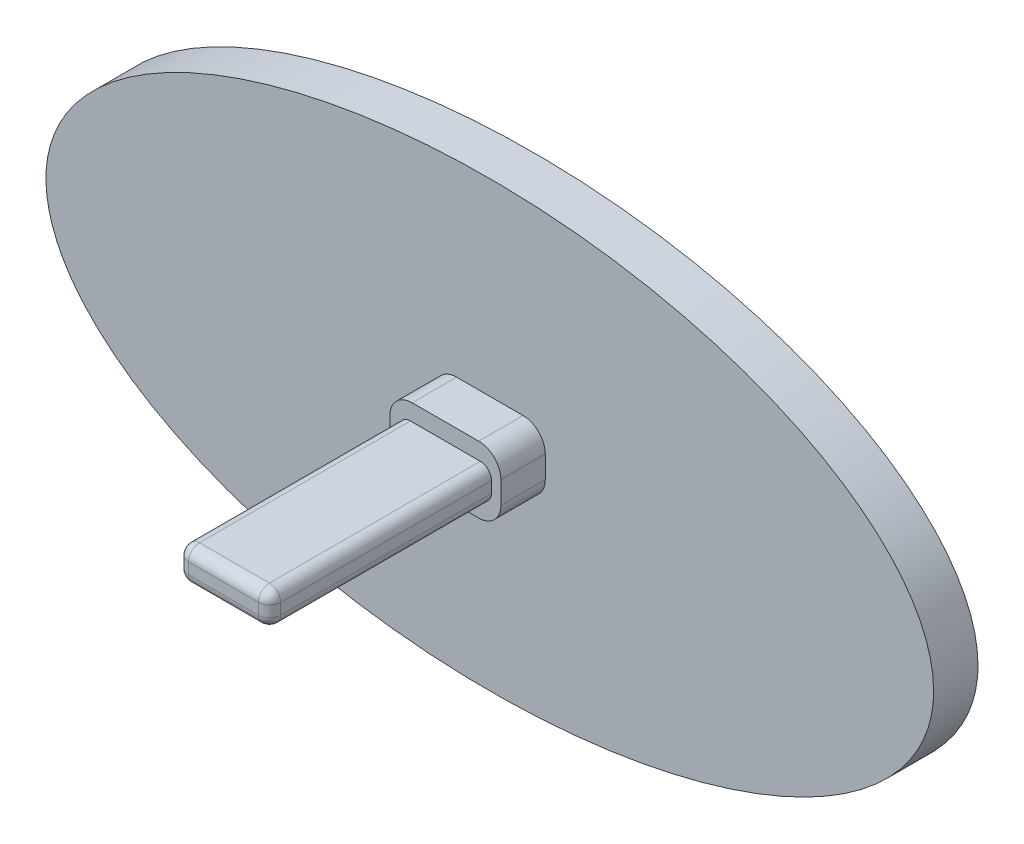
SolidWorks part; units mm, degrees
ref_plane "Front Plane" through (0, 0, 0) normal (0, 0, 1) x (1, 0, 0)
ref_plane "Top Plane" through (0, 0, 0) normal (0, 1, 0) x (1, 0, 0)
ref_plane "Right Plane" through (0, 0, 0) normal (1, 0, 0) x (0, 0, -1)
sketch "Sketch1" plane through (0, 0, 0) normal (0, 0, 1) x (1, 0, 0)
  ellipse E0 centre (0, 0) end of major axis (20, 0) minor radius 10
  dimension "D1" = 20
  dimension "D2" = 20
extrude "Boss-Extrude1" add sketch "Sketch1" along normal blind 2
sketch "Sketch2" plane through (0, 0, 0) normal (0, 1, 0) x (1, 0, 0)
  line L0 (-20, -2) -> (20, -2) construction
  line L1 (-2.5, -4) -> (2.5, -4)
  line L2 (-2.5, -4) -> (-2.5, -2)
  line L3 (-2.5, -2) -> (2.5, -2)
  line L4 (2.5, -4) -> (2.5, -2)
  line L5 (0, -1.1) -> (0, 1.1) construction
  point P6 (0, -4)
  dimension "D1" = 5
  dimension "D2" = 2
extrude "Boss-Extrude2" add sketch "Sketch2" along normal blind 1.5 and the other way blind 1.5
sketch "Sketch3" plane through (0, 0, 4) normal (0, 0, 1) x (1, 0, 0)
  line L1 (-2.075, 0.75) -> (2.075, 0.75)
  line L2 (-2.075, 0.75) -> (-2.075, -0.75)
  line L3 (-2.075, -0.75) -> (2.075, -0.75)
  line L4 (2.075, 0.75) -> (2.075, -0.75)
  line L7 (0, -7.7) -> (0, 7.7) construction
  line L8 (7.7, 0) -> (-7.7, 0) construction
  point P4 (0, 0.75)
  point P6 (2.075, 0)
  dimension "D1" = 1.5
  dimension "D2" = 4.15
extrude "Boss-Extrude3" add sketch "Sketch3" along normal blind 10
fillet "Fillet1" radius 1 4 edges at (-2.5, -1.5, 3) (-2.5, 1.5, 3) (2.5, 1.5, 3) (2.5, -1.5, 3)
fillet "Fillet3" radius 0.5 8 edges at (0, 0.75, 14) (-2.075, 0, 14) (0, -0.75, 14) (2.075, 0, 14) (2.075, 0.75, 9) (2.075, -0.75, 9) (-2.075, 0.75, 9) (-2.075, -0.75, 9)
